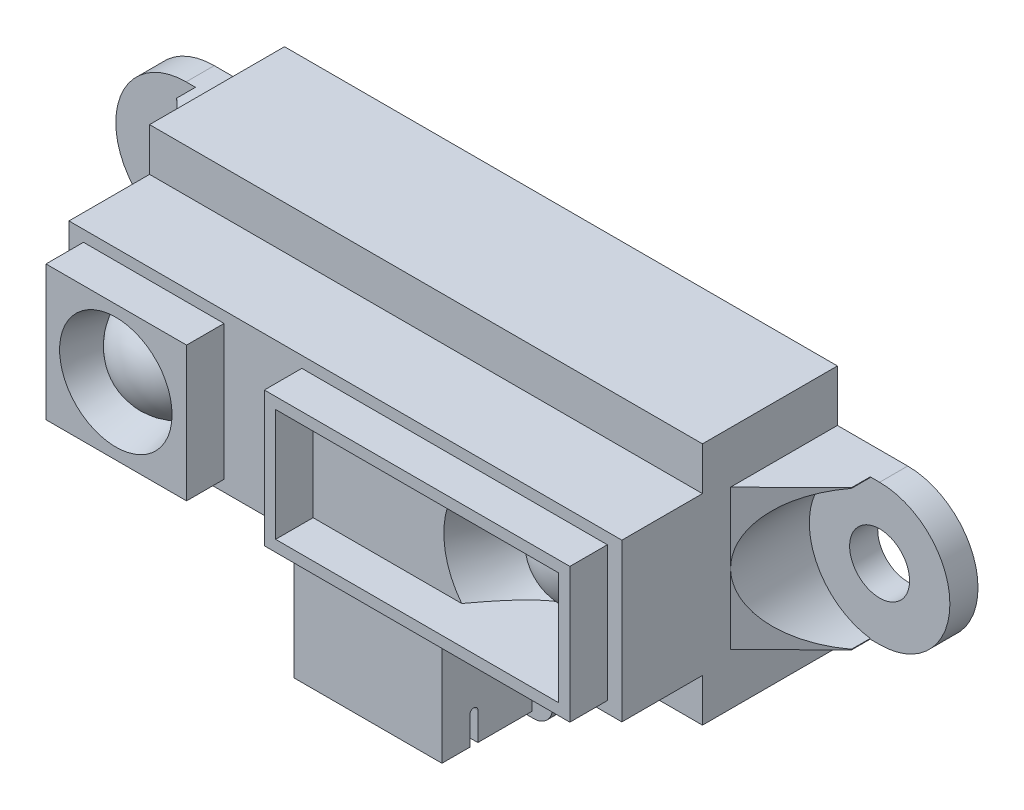
SolidWorks part; units mm, degrees
ref_plane "Front Plane" through (0, 0, 0) normal (0, 0, 1) x (1, 0, 0)
ref_plane "Top Plane" through (0, 0, 0) normal (0, 1, 0) x (1, 0, 0)
ref_plane "Right Plane" through (0, 0, 0) normal (1, 0, 0) x (0, 0, -1)
sketch "Sketch2" plane through (0, 0, 0) normal (0, 0, 1) x (1, 0, 0)
  line L0 (-74.7319, 25.7242) -> (-45.2319, 25.7242)
  line L1 (-74.7319, 22.9742) -> (-78.4819, 22.9742)
  line L2 (-74.7319, 25.7242) -> (-74.7319, 22.9742)
  line L3 (-74.7319, 12.7242) -> (-65.0319, 12.7242)
  line L4 (-65.0319, 15.0242) -> (-65.0319, 12.7242)
  line L5 (-74.7319, 15.4742) -> (-78.4819, 15.4742)
  line L6 (-54.9319, 15.0242) -> (-54.9319, 12.7242)
  line L7 (-54.9319, 12.7242) -> (-45.2319, 12.7242)
  line L8 (-45.2319, 25.7242) -> (-45.2319, 22.9742)
  line L9 (-78.4819, 22.9742) -> (-78.4819, 15.4742) construction
  line L10 (-45.2319, 22.9742) -> (-41.4819, 22.9742)
  line L11 (-65.0319, 15.0242) -> (-54.9319, 15.0242)
  line L12 (-41.4819, 22.9742) -> (-41.4819, 15.4742) construction
  line L13 (-41.4819, 15.4742) -> (-45.2319, 15.4742)
  line L14 (-74.7319, 15.4742) -> (-74.7319, 12.7242)
  line L15 (-45.2319, 15.4742) -> (-45.2319, 12.7242)
  arc A0 (-78.4819, 22.9742) -> (-78.4819, 15.4742) centre (-78.4819, 19.2242) ccw
  arc A1 (-41.4819, 22.9742) -> (-41.4819, 15.4742) centre (-41.4819, 19.2242) cw
  circle A2 centre (-78.4819, 19.2242) radius 1.6
  circle A3 centre (-41.4819, 19.2242) radius 1.6
  dimension "D10" = 3.2
  dimension "D11" = 3.2
  dimension "D1" = 29.5
  dimension "D2" = 13
  dimension "D3" = 13
  dimension "D4" = 2.3
  dimension "D5" = 9.7
  dimension "D6" = 10.1
  dimension "D7" = 3.75
  dimension "D8" = 37
  dimension "D9" = 7.5
  dimension "D12" = 6.5
extrude "Boss-Extrude1" add sketch "Sketch2" along normal blind 7.2
sketch "Sketch4" plane through (0, 12.7242, 0) normal (0, -1, 0) x (1, 0, 0)
  line L0 (-74.7319, 5.7) -> (-77.9819, 2.5)
  line L1 (-74.7319, 7.2) -> (-74.7319, 0) construction
  line L2 (-77.9819, 2.5) -> (-77.9819, 1.5)
  line L3 (-77.9819, 1.5) -> (-84.8304, 1.5)
  line L4 (-84.8304, 1.5) -> (-84.8304, 9.5276)
  line L5 (-84.8304, 9.5276) -> (-74.7319, 9.5276)
  line L6 (-74.7319, 9.5276) -> (-74.7319, 5.7)
  line L7 (-74.7319, 0) -> (-45.2319, 0) construction
  line L8 (-59.9819, 0) -> (-59.9819, 7.2) construction
  line L9 (-65.0319, 7.2) -> (-54.9319, 7.2) construction
  line L10 (-82.2319, 0) -> (-78.4819, 0) construction
  line L11 (-78.4819, 7.2) -> (-78.4819, 0) construction
  line L12 (-74.7319, 7.2) -> (-65.0319, 7.2) construction
  line L13 (-45.2319, 9.5276) -> (-45.2319, 5.7)
  line L14 (-35.1335, 9.5276) -> (-45.2319, 9.5276)
  line L15 (-35.1335, 1.5) -> (-35.1335, 9.5276)
  line L16 (-41.9819, 1.5) -> (-35.1335, 1.5)
  line L17 (-41.9819, 2.5) -> (-41.9819, 1.5)
  line L18 (-45.2319, 5.7) -> (-41.9819, 2.5)
  dimension "D1" = 1.5
  dimension "D2" = 0.5
  dimension "D3" = 1.5
  dimension "D4" = 1
extrude "Cut-Extrude1" cut sketch "Sketch4" against normal through all
sketch "Sketch5" plane through (0, 0, 1.5) normal (0, 0, 1) x (1, 0, 0)
  circle A0 centre (-78.4819, 19.2242) radius 3.75
  circle A1 centre (-41.4819, 19.2242) radius 3.75
  dimension "D1" = 7.5
  dimension "D2" = 7.5
extrude "Cut-Extrude2" cut sketch "Sketch5" along normal through all
sketch "Sketch6" plane through (0, 0, 7.2) normal (0, 0, 1) x (1, 0, 0)
  line L0 (-74.7319, 25.7242) -> (-74.7319, 12.7242) construction
  line L1 (-74.7319, 23.4242) -> (-45.2319, 23.4242)
  line L2 (-74.7319, 23.4242) -> (-74.7319, 15.0242)
  line L3 (-74.7319, 15.0242) -> (-45.2319, 15.0242)
  line L4 (-45.2319, 23.4242) -> (-45.2319, 15.0242)
  line L5 (-45.2319, 12.7242) -> (-45.2319, 25.7242) construction
  line L6 (-45.2319, 25.7242) -> (-74.7319, 25.7242) construction
  line L7 (-65.0319, 15.0242) -> (-54.9319, 15.0242) construction
  dimension "D1" = 2.3
  dimension "D2" = 0
extrude "Boss-Extrude2" add sketch "Sketch6" along normal blind 4.3
sketch "Sketch7" plane through (0, 0, 11.5) normal (0, 0, 1) x (1, 0, 0)
  line L0 (-74.7319, 22.9742) -> (-74.7319, 19.2242) construction
  line L1 (-73.9569, 22.8242) -> (-66.4569, 22.8242)
  line L2 (-73.9569, 22.8242) -> (-73.9569, 15.6242)
  line L3 (-73.9569, 15.6242) -> (-66.4569, 15.6242)
  line L4 (-66.4569, 22.8242) -> (-66.4569, 15.6242)
  line L5 (-62.3069, 22.8242) -> (-46.0069, 22.8242)
  line L6 (-62.3069, 22.8242) -> (-62.3069, 15.6242)
  line L7 (-62.3069, 15.6242) -> (-46.0069, 15.6242)
  line L8 (-46.0069, 22.8242) -> (-46.0069, 15.6242)
  line L9 (-61.7069, 22.2242) -> (-46.6069, 22.2242)
  line L10 (-61.7069, 22.2242) -> (-61.7069, 16.2242)
  line L11 (-61.7069, 16.2242) -> (-46.6069, 16.2242)
  line L12 (-46.6069, 22.2242) -> (-46.6069, 16.2242)
  line L13 (-45.2319, 23.4242) -> (-74.7319, 23.4242) construction
  circle A0 centre (-70.2319, 19.2242) radius 2.5
  dimension "D12" = 5
  dimension "D1" = 7.5
  dimension "D2" = 16.3
  dimension "D3" = 4.15
  dimension "D4" = 0.775
  dimension "D5" = 7.2
  dimension "D6" = 0.6
  dimension "D7" = 7.2
  dimension "D8" = 0.6
  dimension "D9" = 0.6
  dimension "D10" = 0.6
  dimension "D11" = 0.6
  dimension "D13" = 3.6
  dimension "D14" = 4.5
extrude "Boss-Extrude3" add sketch "Sketch7" along normal blind 2
chamfer "Chamfer1" distance 0.5 distance2 2 1 edges at (-67.7319, 19.2242, 13.5) first distance on face at (-70.2069, 19.2242, 13.5)
sketch "Sketch8" plane through (0, 0, 11.5) normal (0, 0, 1) x (1, 0, 0)
  circle A0 centre (-50.2319, 18.9966) radius 2.5
  circle A1 centre (-70.2319, 19.2242) radius 2.5 construction
  dimension "D2" = 5
  dimension "D1" = 20
extrude "Cut-Extrude3" cut sketch "Sketch8" against normal blind 3
chamfer "Chamfer2" distance 2 angle 60 1 edges at (-47.7319, 18.9966, 11.5) first distance on face at (-47.7319, 18.9966, 11.5)
sketch "Sketch9" plane through (0, 0, 0) normal (0, 0, -1) x (-1, 0, 0)
  line L0 (45.2319, 22.9742) -> (45.2319, 25.7242) construction
  line L1 (45.8319, 25.1242) -> (74.1319, 25.1242)
  line L2 (45.8319, 25.1242) -> (45.8319, 13.3242)
  line L3 (45.8319, 13.3242) -> (74.1319, 13.3242)
  line L4 (74.1319, 25.1242) -> (74.1319, 13.3242)
  line L5 (45.2319, 25.7242) -> (74.7319, 25.7242) construction
  line L6 (74.7319, 25.7242) -> (74.7319, 22.9742) construction
  line L7 (74.7319, 12.7242) -> (65.0319, 12.7242) construction
  dimension "D1" = 0.6
  dimension "D2" = 0.6
  dimension "D3" = 0.6
  dimension "D4" = 0.6
extrude "Cut-Extrude4" cut sketch "Sketch9" against normal blind 5.5
sketch "Sketch10" plane through (0, 0, 5.5) normal (0, 0, -1) x (-1, 0, 0)
  line L0 (54.9319, 13.3242) -> (54.9319, 6.8242)
  line L1 (54.9319, 6.8242) -> (65.0319, 6.8242)
  line L2 (65.0319, 6.8242) -> (65.0319, 13.3242)
  line L4 (74.7319, 12.7242) -> (65.0319, 12.7242) construction
  line L8 (65.0319, 15.0242) -> (65.0319, 13.3242)
  line L9 (65.0319, 13.3242) -> (74.1319, 13.3242)
  line L10 (74.1319, 13.3242) -> (74.1319, 25.1242)
  line L11 (74.1319, 25.1242) -> (45.8319, 25.1242)
  line L12 (45.8319, 25.1242) -> (45.8319, 13.3242)
  line L13 (45.8319, 13.3242) -> (54.9319, 13.3242)
  line L14 (54.9319, 13.3242) -> (54.9319, 15.0242)
  line L15 (54.9319, 15.0242) -> (65.0319, 15.0242)
  line L17 (65.0319, 13.3242) -> (74.1319, 13.3242)
  line L18 (74.1319, 13.3242) -> (74.1319, 25.1242)
  line L19 (74.1319, 25.1242) -> (45.8319, 25.1242)
  line L20 (45.8319, 25.1242) -> (45.8319, 13.3242)
  line L21 (45.8319, 13.3242) -> (54.9319, 13.3242)
  dimension "D2" = 5.9
  dimension "D1" = 0
extrude "Boss-Extrude4" add sketch "Sketch10" along normal blind 1.2
ref_point "Point1"
ref_point "Point2"
ref_axis "Axis1" through (-70.2319, 19.2242, 11.5) along (0, 0, 1)
ref_axis "Axis2" through (-50.2319, 18.9966, 8.5) along (0, 0, 1)
ref_plane "Plane1" through (0, 18.9966, 0) normal (0, 1, 0) x (1, 0, 0)
ref_plane "Plane2" through (0, 19.2242, 0) normal (0, -1, 0) x (-1, 0, 0)
sketch "Sketch11" plane through (0, 18.9966, 0) normal (0, 1, 0) x (1, 0, 0)
  line L0 (-52.9999, -8.5) -> (-47.464, -8.5) construction
  line L1 (-50.2319, -8.5) -> (-47.464, -8.5)
  line L2 (-50.2319, -8.5) -> (-50.2319, -10.5)
  line L3 (-50.2319, -10.5) -> (-51.57, -10.5) construction
  line L4 (-50.2319, -8.5) -> (-50.2319, -11.0836) construction
  arc A0 (-50.2319, -10.5) -> (-47.464, -8.5) centre (-50.2319, -7.5846) ccw
  dimension "D1" = 2
revolve "Revolve1" add sketch "Sketch11" angle 360 about axis through (-50.2319, 18.9966, 8.5) along (0, 0, 1)
sketch "Sketch14" plane through (0, 19.2242, 0) normal (0, -1, 0) x (-1, 0, 0)
  line L0 (67.7319, -11.5) -> (72.7319, -11.5) construction
  line L1 (70.2319, -11.5) -> (72.7319, -11.5)
  line L2 (70.2319, -11.5) -> (70.2319, -13)
  line L3 (70.2319, -13) -> (68.5541, -13) construction
  line L4 (70.2319, -11.5) -> (70.2319, -13.8335) construction
  arc A0 (70.2319, -13) -> (72.7319, -11.5) centre (70.2319, -10.1667) ccw
  dimension "D1" = 1.5
revolve "Revolve2" add sketch "Sketch14" angle 360 about axis through (-70.2319, 19.2242, 11.5) along (0, 0, 1)
fillet "Fillet1" radius 1 2 edges at (-54.9319, 6.8242, 4.9) (-65.0319, 6.8242, 4.9)
ref_plane "Plane3" through (-59.9819, 0, 0) normal (1, 0, 0) x (0, 0, -1)
sketch "Sketch16" plane through (-59.9819, 0, 0) normal (1, 0, 0) x (0, 0, -1)
  line L0 (-8.385, 8.6131) -> (-8.385, 7.1131)
  line L1 (-8.385, 7.1131) -> (-5.5, 7.1131)
  line L2 (-5.5, 7.1131) -> (-5.5, 14.7131)
  line L3 (-5.5, 14.7131) -> (-7.5, 14.7131)
  line L4 (-7.5, 14.7131) -> (-9.1, 13.1131)
  line L5 (-9.1, 13.1131) -> (-10.3, 13.1131)
  line L6 (-10.3, 13.1131) -> (-10.3, 7.1131)
  line L7 (-10.3, 7.1131) -> (-8.815, 7.1131)
  line L8 (-8.815, 7.1131) -> (-8.815, 8.6131)
  line L9 (-5.5, 7.8242) -> (-5.5, 12.7242) construction
  arc A0 (-8.385, 8.6131) -> (-8.815, 8.6131) centre (-8.6, 8.6131) ccw
  dimension "D1" = 7.6
  dimension "D2" = 6
  dimension "D3" = 1.7
  dimension "D4" = 2
  dimension "D5" = 1.2
  dimension "D6" = 4.8
  dimension "D7" = 1.5
extrude "Boss-Extrude5" add sketch "Sketch16" along normal blind 3.95 and the other way blind 3.95
sketch "Sketch17" plane through (0, 7.1131, 0) normal (0, -1, 0) x (1, 0, 0)
  line L0 (-63.9319, 10.3) -> (-56.0319, 10.3) construction
  line L1 (-63.4319, 9.8) -> (-56.5319, 9.8)
  line L2 (-63.4319, 9.8) -> (-63.4319, 6)
  line L3 (-63.4319, 6) -> (-56.5319, 6)
  line L4 (-56.5319, 9.8) -> (-56.5319, 6)
  line L5 (-63.9319, 5.5) -> (-56.0319, 5.5) construction
  line L6 (-56.0319, 10.3) -> (-56.0319, 8.815) construction
  line L7 (-63.9319, 10.3) -> (-63.9319, 8.815) construction
  dimension "D1" = 0.5
  dimension "D2" = 0.5
  dimension "D3" = 0.5
  dimension "D4" = 0.5
extrude "Cut-Extrude5" cut sketch "Sketch17" against normal blind 5.8
sketch "Sketch18" plane through (0, 12.9131, 0) normal (0, -1, 0) x (1, 0, 0)
  line L2 (-63.4319, 7.9) -> (-56.5319, 7.9) construction
  line L3 (-63.4319, 9.8) -> (-63.4319, 6) construction
  line L4 (-56.5319, 6) -> (-56.5319, 9.8) construction
  circle A0 centre (-59.9819, 7.9) radius 0.5
  circle A1 centre (-57.9819, 7.9) radius 0.5
  circle A2 centre (-61.9819, 7.9) radius 0.5
  dimension "D1" = 1
  dimension "D2" = 2
  dimension "D3" = 2
extrude "Boss-Extrude6" add sketch "Sketch18" along normal blind 5.5
fillet "Fillet2" radius 0.5 3 edges at (-57.9819, 7.4131, 7.4) (-59.9819, 7.4131, 7.4) (-61.9819, 7.4131, 7.4)
